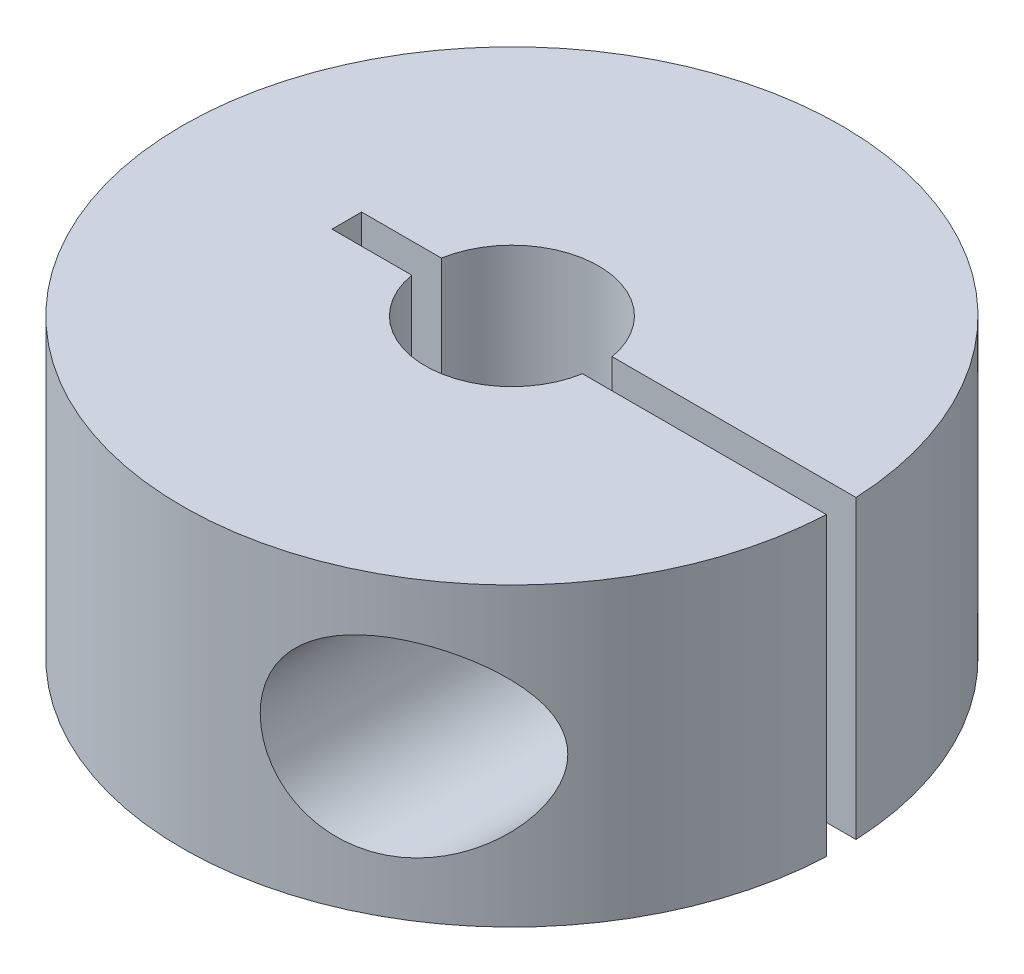
SolidWorks part; units mm, degrees
ref_plane "Front Plane" through (0, 0, 0) normal (0, 0, 1) x (1, 0, 0)
ref_plane "Top Plane" through (0, 0, 0) normal (0, 1, 0) x (1, 0, 0)
ref_plane "Right Plane" through (0, 0, 0) normal (1, 0, 0) x (0, 0, -1)
sketch "Sketch1" plane through (0, 0, 0) normal (0, 1, 0) x (1, 0, 0)
  circle A0 centre (0, 0) radius 11.125
  dimension "D1" = 22.25
extrude "Boss-Extrude1" add sketch "Sketch1" along normal blind 10
ref_plane "Plane1" through (0, 0, -3) normal (0, 0, 1) x (1, 0, 0)
sketch "Sketch2" plane through (0, 0, -3) normal (0, 0, 1) x (1, 0, 0)
  line L0 (0, 5) -> (11.125, 5) construction
  line L1 (11.125, 10) -> (-11.125, 10) construction
  line L2 (0, 0) -> (0, 10) construction
  line L3 (11.125, 0) -> (11.125, 10) construction
  line L5 (4.3581, 2.8954) -> (6.783, 2.9047)
  line L6 (6.783, 2.9047) -> (7.9874, 5.0093)
  line L7 (7.9874, 5.0093) -> (6.7669, 7.1046)
  line L8 (6.7669, 7.1046) -> (4.342, 7.0953)
  line L9 (4.342, 7.0953) -> (3.1376, 4.9907)
  line L10 (3.1376, 4.9907) -> (4.3581, 2.8954)
  circle A0 centre (5.5625, 5) radius 2.1 construction
  point P1 (0, 10)
  point P9 (5.5625, 5)
  dimension "D1" = 4.2
  dimension "D2" = 2.4249
extrude "Cut-Extrude1" cut sketch "Sketch2" against normal through all
sketch "Sketch3" plane through (0, 0, 0) normal (0, 1, 0) x (1, 0, 0)
  line L0 (-5.5735, 0.5) -> (-5.5735, -0.5)
  line L5 (-5.5735, -0.5) -> (11.4265, -0.5)
  line L6 (11.4265, -0.5) -> (11.4265, 0.5)
  line L12 (11.4265, 0.5) -> (-5.5735, 0.5)
  line L13 (-5.5735, 0) -> (11.4265, 0) construction
  point P3 (-0.5735, 0.5)
  point P7 (0, 0)
  dimension "D1" = 5
  dimension "D2" = 12
  dimension "D3" = 1
extrude "Cut-Extrude2" cut sketch "Sketch3" along normal through all
ref_plane "Plane2" through (0, 0, 4.6) normal (0, 0, 1) x (1, 0, 0)
sketch "Sketch6" plane through (0, 0, 4.6) normal (0, 0, 1) x (1, 0, 0)
  line L0 (0, 5) -> (11.125, 5) construction
  point P0 (5.5625, 5)
hole_wizard "CBORE for M2 Hex Head Machine Screw1" positions "Sketch6" profile "Sketch7" counterbore size "M2" standard "ANSI Metric" end condition through all
sketch "Sketch7" plane through (5.5625, 5, 4.6) normal (1, 0, 0) x (0, -1, 0)
  line L0 (0, 0) -> (0, 15.725)
  line L1 (0, 15.725) -> (1.2, 15.725)
  line L3 (1.2, 15.725) -> (1.2, 1.6)
  line L4 (1.2, 1.6) -> (3.19, 1.6)
  line L5 (3.19, 1.6) -> (3.19, 0)
  line L7 (3.19, 0) -> (0, 0)
  line L11 (0, -6.35) -> (0, 107.95) construction
  dimension "Thru Hole Dia." = 2.4
  dimension "Thru Hole Depth" = 15.725
  dimension "C'Bore Dia." = 6.38
  dimension "C'Bore Depth" = 1.6
sketch "Sketch8" plane through (0, 0, 4.6) normal (0, 0, 1) x (1, 0, 0)
  circle A0 centre (5.5625, 5) radius 3.19
  dimension "D1" = 6.38
extrude "Cut-Extrude3" cut sketch "Sketch8" along normal through all
sketch "Sketch9" plane through (0, 0, 0) normal (0, 1, 0) x (1, 0, 0)
  circle A0 centre (0, 0) radius 2.925
  dimension "AxleHoleDiameter" = 5.85
extrude "Cut-Extrude4" cut sketch "Sketch9" along normal through all both and the other way through all
